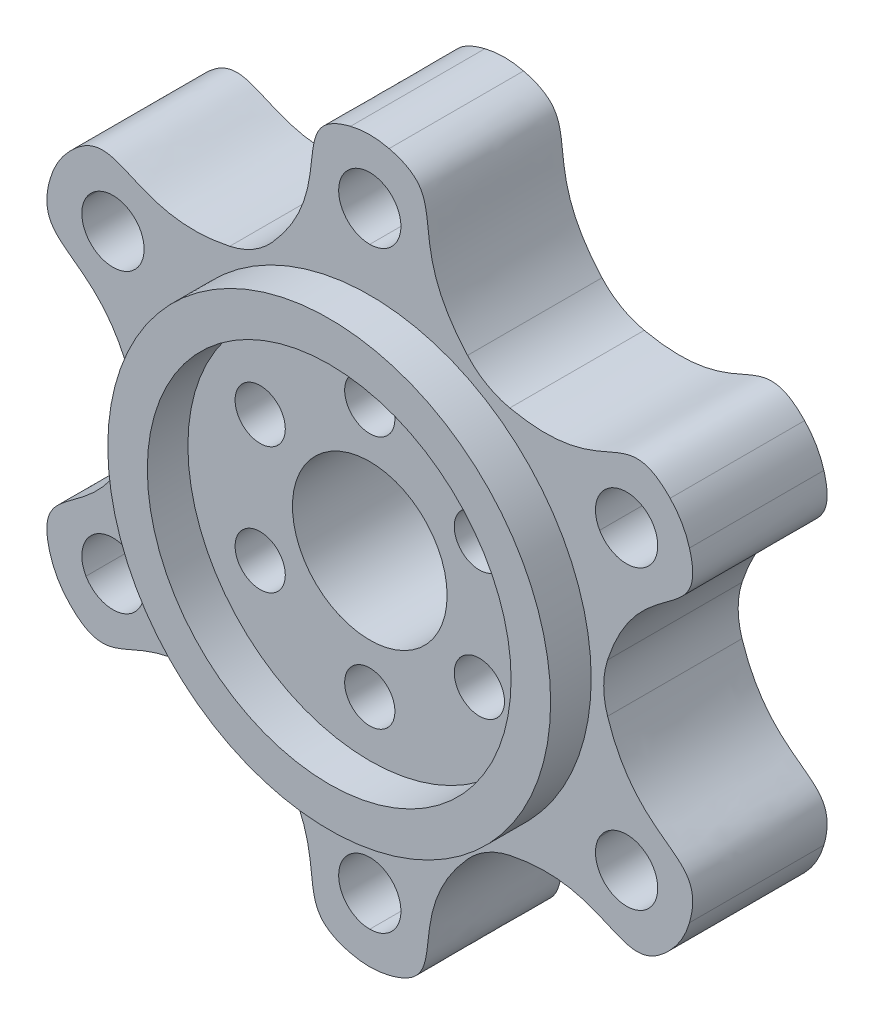
SolidWorks part; units mm, degrees
ref_plane "Front Plane" through (0, 0, 0) normal (0, 0, 1) x (1, 0, 0)
ref_plane "Top Plane" through (0, 0, 0) normal (0, 1, 0) x (1, 0, 0)
ref_plane "Right Plane" through (0, 0, 0) normal (1, 0, 0) x (0, 0, -1)
sketch "Sketch1" plane through (0, 0, 0) normal (0, 0, 1) x (1, 0, 0)
  line L0 (0, -55) -> (0, 55) construction
  line L1 (0, 0) -> (0, 45.72) construction
  circle A0 centre (0, 0) radius 9.779
  circle A1 centre (0, 0) radius 45.72
  circle A2 centre (0, 16.002) radius 3.175
  circle A3 centre (13.8581, 8.001) radius 3.175
  circle A4 centre (13.8581, -8.001) radius 3.175
  circle A5 centre (0, -16.002) radius 3.175
  circle A6 centre (-13.8581, -8.001) radius 3.175
  circle A7 centre (-13.8581, 8.001) radius 3.175
  circle A8 centre (0, 37.5) radius 3.937
  circle A10 centre (32.476, 18.75) radius 3.937
  circle A11 centre (32.476, -18.75) radius 3.937
  circle A12 centre (0, -37.5) radius 3.937
  circle A13 centre (-32.476, -18.75) radius 3.937
  circle A14 centre (-32.476, 18.75) radius 3.937
  point P21 (0, 0)
  point P36 (0, 0)
  dimension "D1" = 19.558
  dimension "D2" = 91.44
  dimension "D3" = 6.35
  dimension "D6" = 7.874
  dimension "D4" = 16.002
  dimension "D8" = 37.5
  dimension "D5" = 6
  dimension "D7" = 6
extrude "Boss-Extrude3" add sketch "Sketch1" along normal blind 17
sketch "Sketch2" plane through (0, 0, 17) normal (0, 0, 1) x (1, 0, 0)
  line L0 (0, -9.35) -> (0, 9.35) construction
  line L1 (-32.476, 18.75) -> (0, 37.5) construction
  line L2 (-16.238, 28.125) -> (-4.8895, 8.4689) construction
  line L3 (16.1981, 28.148) -> (4.8496, 8.4918) construction
  line L6 (32.476, -18.75) -> (32.476, 18.75) construction
  line L7 (32.476, 18.75) -> (0, 37.5) construction
  line L8 (9.35, 0) -> (-9.35, 0) construction
  circle A0 centre (0, 0) radius 27.94 construction
  circle A1 centre (0, 0) radius 45.72 construction
  circle A2 centre (0, 0) radius 9.779 construction
  circle A3 centre (0, 0) radius 45.72
  spline S0 degree 3 poles (-14.625, 25.3312) (-1.5745, 37.1177) (-13.1193, 43.9586) (0, 45.72) knots 0 0 0 0 1 1 1 1
  spline S1 degree 3 poles (14.625, 25.3312) (1.5745, 37.1177) (13.1193, 43.9586) (0, 45.72) knots 0 0 0 0 1 1 1 1
  spline S2 degree 3 poles (-29.25, 0) (-32.9321, 17.1953) (-44.6289, 10.6177) (-39.5947, 22.86) knots 0 0 0 0 1 1 1 1
  spline S3 degree 3 poles (-14.625, 25.3312) (-31.3576, 19.9224) (-31.5096, 33.3409) (-39.5947, 22.86) knots 0 0 0 0 1 1 1 1
  spline S4 degree 3 poles (-14.625, -25.3312) (-31.3576, -19.9224) (-31.5096, -33.3409) (-39.5947, -22.86) knots 0 0 0 0 1 1 1 1
  spline S5 degree 3 poles (-29.25, 0) (-32.9321, -17.1953) (-44.6289, -10.6177) (-39.5947, -22.86) knots 0 0 0 0 1 1 1 1
  spline S6 degree 3 poles (14.625, -25.3312) (31.3576, -19.9224) (31.5096, -33.3409) (39.5947, -22.86) knots 0 0 0 0 1 1 1 1
  spline S7 degree 3 poles (29.25, 0) (32.9321, -17.1953) (44.6289, -10.6177) (39.5947, -22.86) knots 0 0 0 0 1 1 1 1
  spline S8 degree 3 poles (14.625, -25.3312) (1.5745, -37.1177) (13.1193, -43.9586) (0, -45.72) knots 0 0 0 0 1 1 1 1
  spline S9 degree 3 poles (-14.625, -25.3312) (-1.5745, -37.1177) (-13.1193, -43.9586) (0, -45.72) knots 0 0 0 0 1 1 1 1
  spline S10 degree 3 poles (29.25, 0) (32.9321, 17.1953) (44.6289, 10.6177) (39.5947, 22.86) knots 0 0 0 0 1 1 1 1
  spline S11 degree 3 poles (14.625, 25.3312) (31.3576, 19.9224) (31.5096, 33.3409) (39.5947, 22.86) knots 0 0 0 0 1 1 1 1
  point P5 (-16.238, 28.125)
  point P6 (16.1981, 28.148)
  circle M8 centre (0, 0) radius 45.72
  dimension "D1" = 55.88
  dimension "D2" = 18.796
  dimension "D3" = 29.25
extrude "Cut-Extrude1" cut sketch "Sketch2" against normal blind 22.86 contours S1 S11 M8 | S5 S2 A3 | S10 S7 A3 | S6 S8 A3 | S9 S4 M8 | S3 S0 M8 region at (38.672, 0, 17) region at (19.336, 33.4909, 17) region at (19.336, -33.4909, 17) region at (-19.336, 33.4909, 17) region at (-19.336, -33.4909, 17) region at (-38.672, 0, 17)
sketch "Sketch4" plane through (0, 0, 17) normal (0, 0, 1) x (1, 0, 0)
  circle A0 centre (0, 0) radius 9.779 construction
  circle A1 centre (0, 0) radius 9.779 construction
  circle A2 centre (0, 0) radius 28
  circle A3 centre (0, 0) radius 23
  dimension "D1" = 56
  dimension "D2" = 46
extrude "Boss-Extrude4" add sketch "Sketch4" along normal blind 5.1308 contours A2 | A3
ref_plane "Plane1" through (0, 0, 0) normal (1, 0, 0) x (0, 0, -1)
ref_plane "Plane2" through (0, 0, 0) normal (-0.5, -0.866, 0) x (-0.866, 0.5, 0)
ref_plane "Plane3" through (0, 0, 0) normal (-0.5, 0.866, 0) x (0.866, 0.5, 0)
split line "Split Line1"
split line "Split Line2"
split line "Split Line3"
ref_axis "Axis1" through (0, 0, 17) along (0, 0, -1)
fillet "Fillet1" radius 10 12 edges at (29.25, 0, 8.5) (39.5947, -22.86, 8.5) (0, -45.72, 8.5) (14.625, -25.3312, 8.5) (-14.625, -25.3312, 8.5) (-39.5947, -22.86, 8.5) (-29.25, 0, 8.5) (-39.5947, 22.86, 8.5) (-14.625, 25.3312, 8.5) (14.625, 25.3312, 8.5) (39.5947, 22.86, 8.5) (0, 45.72, 8.5)
